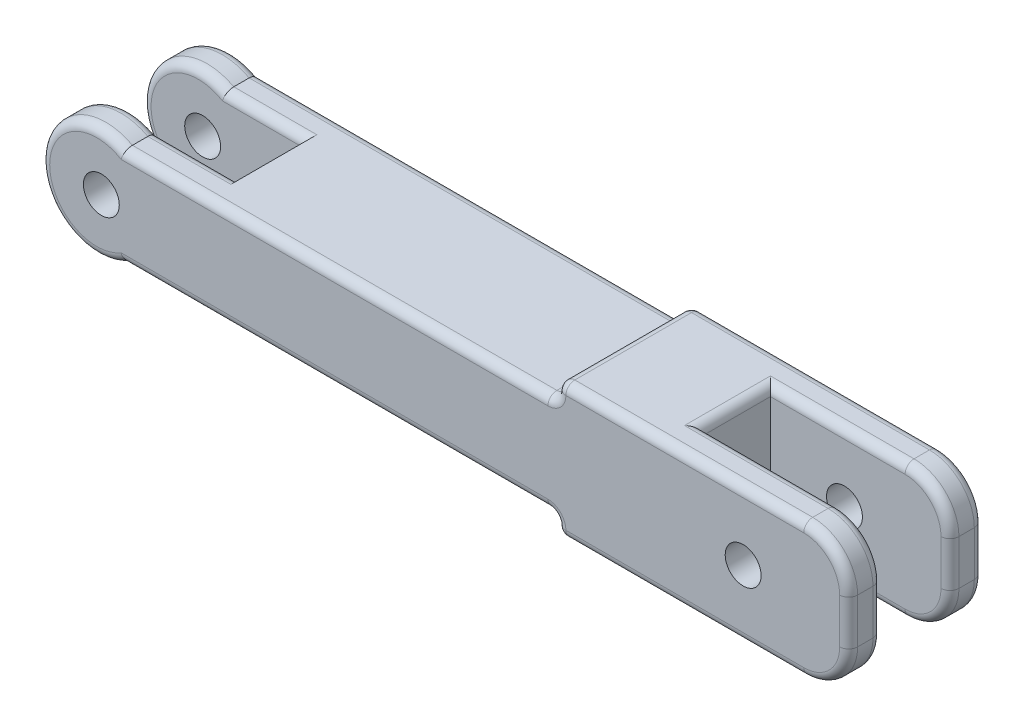
SolidWorks part; units mm, degrees
ref_plane "Alzado" through (0, 0, 0) normal (0, 0, 1) x (1, 0, 0)
ref_plane "Planta" through (0, 0, 0) normal (0, 1, 0) x (1, 0, 0)
ref_plane "Vista lateral" through (0, 0, 0) normal (1, 0, 0) x (0, 0, -1)
sketch "Croquis1" plane through (0, 0, 0) normal (0, 0, 1) x (1, 0, 0)
  line L4 (90, -15) -> (90, 15)
  line L9 (-25, 11) -> (25, 11)
  line L10 (25, 15) -> (25, 11)
  line L11 (25, -15) -> (90, -15)
  line L14 (25, -15) -> (25, -11)
  line L15 (-25, -11) -> (25, -11)
  line L16 (25, 15) -> (90, 15)
  line L17 (-25, 11) -> (-71.5628, 11)
  line L19 (-25, -11) -> (-71.5628, -11)
  arc A0 (-71.5628, 11) -> (-71.5628, -11) centre (-77.5, 0) ccw
  point P0 (0, 0)
  point P8 (0, 15)
  dimension "D3" = 50
  dimension "D4" = 12.5
  dimension "D1" = 77.5
  dimension "D2" = 30
  dimension "D5" = 4
  dimension "D6" = 11
extrude "Saliente-Extruir1" add sketch "Croquis1" along normal blind 30
fillet "Redondeo1" radius 10 2 edges at (90, -15, 15) (90, 15, 15)
sketch "Croquis2" plane through (0, 11, 0) normal (0, 1, 0) x (1, 0, 0)
  line L0 (-71.5628, -30) -> (-71.5628, 0) construction
  line L1 (-90.0646, -7.425) -> (-53.061, -7.425)
  line L2 (-90.0646, -7.425) -> (-90.0646, -22.575)
  line L3 (-90.0646, -22.575) -> (-53.061, -22.575)
  line L4 (-53.061, -7.425) -> (-53.061, -22.575)
  line L5 (-90.0646, -7.425) -> (-53.061, -22.575) construction
  line L6 (-90.0646, -22.575) -> (-53.061, -7.425) construction
  point P0 (-71.5628, -15)
  dimension "D1" = 15.15
extrude "Cortar-Extruir1" cut sketch "Croquis2" against normal through all and the other way through all
sketch "Croquis3" plane through (0, 0, 30) normal (0, 0, 1) x (1, 0, 0)
  circle A0 centre (-76.5, 0) radius 4
  arc A1 (-71.5628, 11) -> (-71.5628, -11) centre (-77.5, 0) ccw construction
  point P5 (-90, 0)
  dimension "D1" = 13.5
extrude "Cortar-Extruir2" cut sketch "Croquis3" against normal through all
sketch "Croquis4" plane through (0, 15, 0) normal (0, 1, 0) x (1, 0, 0)
  line L0 (80, -30) -> (80, 0) construction
  line L1 (110, -7.425) -> (50, -7.425)
  line L2 (110, -7.425) -> (110, -22.575)
  line L3 (110, -22.575) -> (50, -22.575)
  line L4 (50, -7.425) -> (50, -22.575)
  line L5 (110, -7.425) -> (50, -22.575) construction
  line L6 (110, -22.575) -> (50, -7.425) construction
  line L7 (90, 0) -> (90, -30) construction
  point P0 (80, -15)
  dimension "D1" = 15.15
  dimension "D2" = 40
extrude "Cortar-Extruir3" cut sketch "Croquis4" against normal through all and the other way through all
sketch "Croquis5" plane through (0, 0, 0) normal (0, 0, -1) x (-1, 0, 0)
  line L0 (-90, -5) -> (-90, 5) construction
  circle A0 centre (-66.5, 0) radius 4
  dimension "D1" = 23.5
extrude "Cortar-Extruir4" cut sketch "Croquis5" against normal through all
fillet "Redondeo2" radius 2 38 edges at (52.5, -15, 0) (87.0711, -12.0711, 0) (90, 0, 0) (87.0711, 12.0711, 0) (65, 15, 7.425) (87.0711, 12.0711, 7.425) (90, 0, 7.425) (87.0711, -12.0711, 7.425) (65, -15, 22.575) (87.0711, -12.0711, 22.575) (90, 0, 22.575) (87.0711, 12.0711, 22.575) (52.5, 15, 30) (87.0711, 12.0711, 30) (90, 0, 30) (87.0711, -12.0711, 30) (-23.2814, -11, 0) (-90, 0, 0) (-23.2814, 11, 0) (52.5, 15, 0) (65, -15, 7.425) (50, -15, 15) (50, 15, 15) (65, 15, 22.575) (-90, 0, 30) (-23.2814, 11, 30) (52.5, -15, 30) (-23.2814, -11, 30) (25, -15, 15) (25, -11, 15) (25, 15, 15) (25, 11, 15) (-90, 0, 7.425) (-62.3119, 11, 7.425) (-62.3119, -11, 7.425) (-62.3119, -11, 22.575) (-90, 0, 22.575) (-62.3119, 11, 22.575)
